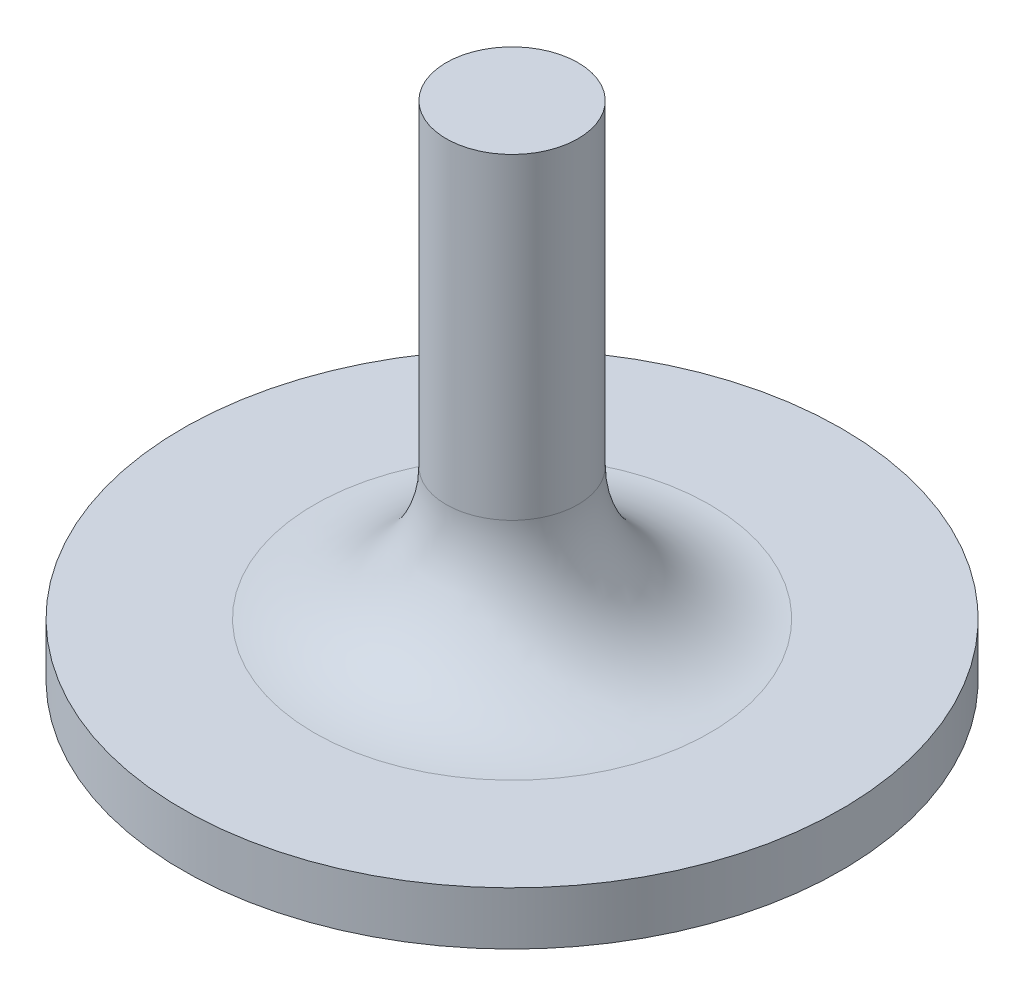
SolidWorks part; units mm, degrees
material "PS HI"
ref_plane "Front Plane" through (0, 0, 0) normal (0, 0, 1) x (1, 0, 0)
ref_plane "Top Plane" through (0, 0, 0) normal (0, 1, 0) x (1, 0, 0)
ref_plane "Right Plane" through (0, 0, 0) normal (1, 0, 0) x (0, 0, -1)
sketch "Sketch1" plane through (0, 0, 0) normal (1, 0, 0) x (0, 0, -1)
  line L0 (0, 0) -> (5, 10.7225)
  line L1 (0, 0) -> (0, 50)
  line L2 (0, 55) -> (0, -55) construction
  line L3 (0, 50) -> (5, 50)
  line L4 (5, 50) -> (5, 15.965)
  line L5 (5, 15.965) -> (25, 15.965)
  line L6 (25, 15.965) -> (25, 11.9419)
  line L7 (25, 11.9419) -> (5, 11.9419)
  line L8 (5, 11.9419) -> (5, 10.7225)
  dimension "D1" = 50
  dimension "D2" = 5
  dimension "D3" = 25
  dimension "D4" = 25
  dimension "D5" = 4.0231
  dimension "D6" = 34.035
revolve "Revolve1" add sketch "Sketch1" angle 360 about L1 other way angle 360
fillet "Fillet1" radius 25 1 edges at (0, 11.9419, -5)
fillet "Fillet12" radius 10 1 edges at (0, 15.965, -5)
